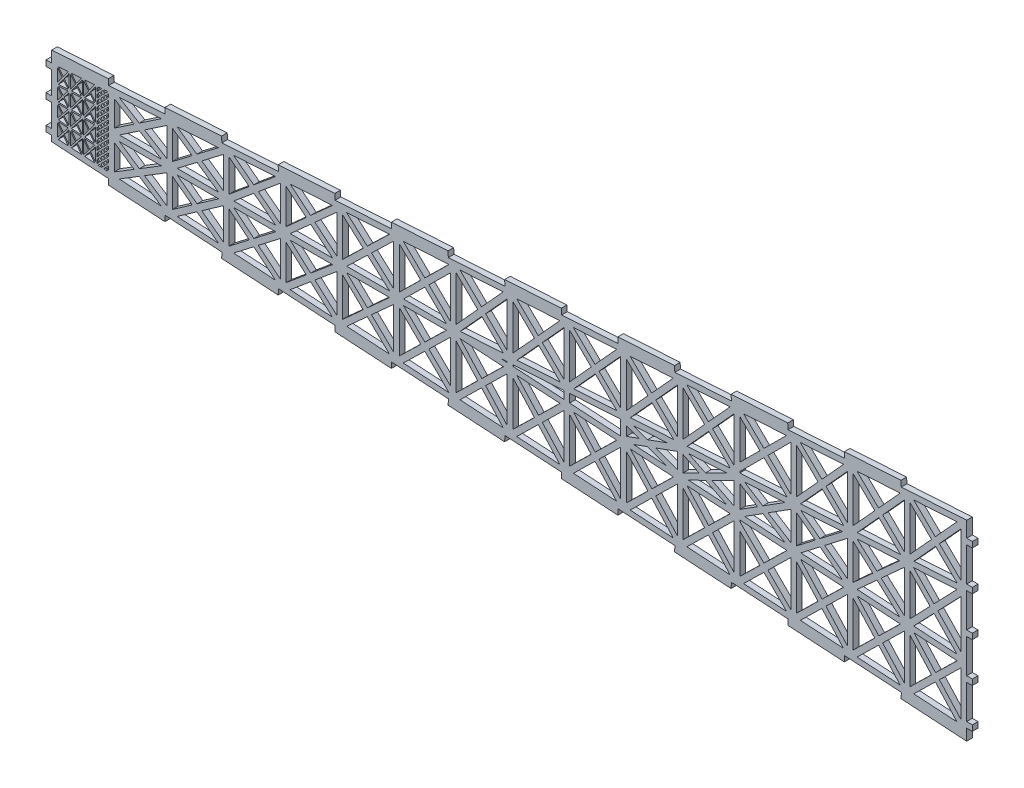
SolidWorks part; units mm, degrees
ref_plane "Front Plane" through (0, 0, 0) normal (0, 0, 1) x (1, 0, 0)
ref_plane "Top Plane" through (0, 0, 0) normal (0, 1, 0) x (1, 0, 0)
ref_plane "Right Plane" through (0, 0, 0) normal (1, 0, 0) x (0, 0, -1)
sketch "Sketch1" plane through (0, 0, 0) normal (0, 0, 1) x (1, 0, 0)
  line L1309 (16.6005, 125.1495) -> (19.3027, 128.3463)
  line L1310 (19.3027, 128.3463) -> (19.3027, 121.7873)
  line L1311 (19.3027, 121.7873) -> (16.6005, 125.1495)
  line L1312 (13.0834, 128.3286) -> (15.6287, 125.1616)
  line L1313 (15.6287, 125.1616) -> (13.0834, 122.1503)
  line L1314 (13.0834, 122.1503) -> (13.0834, 128.3286)
  line L1315 (18.7967, 121.2196) -> (13.5502, 121.5408)
  line L1316 (13.5502, 121.5408) -> (16.1073, 124.566)
  line L1317 (16.1073, 124.566) -> (18.7967, 121.2196)
  line L1318 (13.5645, 128.9272) -> (18.8117, 128.9272)
  line L1319 (18.8117, 128.9272) -> (16.1219, 125.7451)
  line L1320 (16.1219, 125.7451) -> (13.5645, 128.9272)
  line L1321 (16.664, 116.523) -> (19.3027, 119.8354)
  line L1322 (19.3027, 119.8354) -> (19.3027, 112.8875)
  line L1323 (19.3027, 112.8875) -> (16.664, 116.523)
  line L1324 (13.0834, 120.1796) -> (15.722, 116.5441)
  line L1325 (15.722, 116.5441) -> (13.0834, 113.2317)
  line L1326 (13.0834, 113.2317) -> (13.0834, 120.1796)
  line L1327 (13.5683, 120.7883) -> (18.8455, 120.4653)
  line L1328 (18.8455, 120.4653) -> (16.2069, 117.1528)
  line L1329 (16.2069, 117.1528) -> (13.5683, 120.7883)
  line L1330 (18.8178, 112.2788) -> (13.5405, 112.6018)
  line L1331 (13.5405, 112.6018) -> (16.1791, 115.9143)
  line L1332 (16.1791, 115.9143) -> (18.8178, 112.2788)
  line L1333 (23.6334, 116.0963) -> (26.272, 119.4087)
  line L1334 (26.272, 119.4087) -> (26.272, 112.4608)
  line L1335 (26.272, 112.4608) -> (23.6334, 116.0963)
  line L1336 (22.6913, 116.1174) -> (20.0527, 112.805)
  line L1337 (20.0527, 112.805) -> (20.0527, 119.7529)
  line L1338 (20.0527, 119.7529) -> (22.6913, 116.1174)
  line L1339 (20.5376, 120.3617) -> (25.8148, 120.0386)
  line L1340 (25.8148, 120.0386) -> (23.1762, 116.7262)
  line L1341 (23.1762, 116.7262) -> (20.5376, 120.3617)
  line L1342 (25.7871, 111.8521) -> (20.5098, 112.1752)
  line L1343 (20.5098, 112.1752) -> (23.1485, 115.4876)
  line L1344 (23.1485, 115.4876) -> (25.7871, 111.8521)
  line L1345 (23.5637, 124.9366) -> (26.272, 128.3265)
  line L1346 (26.272, 128.3265) -> (26.272, 121.3809)
  line L1347 (26.272, 121.3809) -> (23.5637, 124.9366)
  line L1348 (22.6125, 124.9476) -> (20.0527, 121.7435)
  line L1349 (20.0527, 121.7435) -> (20.0527, 128.3084)
  line L1350 (20.0527, 128.3084) -> (22.6125, 124.9476)
  line L1351 (25.7775, 120.7923) -> (20.5103, 121.1147)
  line L1352 (20.5103, 121.1147) -> (23.081, 124.3325)
  line L1353 (23.081, 124.3325) -> (25.7775, 120.7923)
  line L1354 (20.5241, 128.9272) -> (25.792, 128.9272)
  line L1355 (25.792, 128.9272) -> (23.0952, 125.5517)
  line L1356 (23.0952, 125.5517) -> (20.5241, 128.9272)
  line L1357 (30.5278, 124.7236) -> (33.2413, 128.3062)
  line L1358 (33.2413, 128.3062) -> (33.2413, 120.9749)
  line L1359 (33.2413, 120.9749) -> (30.5278, 124.7236)
  line L1360 (29.5946, 124.7337) -> (27.022, 121.3372)
  line L1361 (27.022, 121.3372) -> (27.022, 128.2877)
  line L1362 (27.022, 128.2877) -> (29.5946, 124.7337)
  line L1363 (32.7569, 120.365) -> (27.4716, 120.6886)
  line L1364 (27.4716, 120.6886) -> (30.0544, 124.0985)
  line L1365 (30.0544, 124.0985) -> (32.7569, 120.365)
  line L1366 (27.4849, 128.9272) -> (32.7709, 128.9272)
  line L1367 (32.7709, 128.9272) -> (30.068, 125.3587)
  line L1368 (30.068, 125.3587) -> (27.4849, 128.9272)
  line L1369 (30.6027, 115.6697) -> (33.2413, 118.9821)
  line L1370 (33.2413, 118.9821) -> (33.2413, 112.0342)
  line L1371 (33.2413, 112.0342) -> (30.6027, 115.6697)
  line L1372 (29.6606, 115.6908) -> (27.022, 112.3784)
  line L1373 (27.022, 112.3784) -> (27.022, 119.3263)
  line L1374 (27.022, 119.3263) -> (29.6606, 115.6908)
  line L1375 (27.5069, 119.935) -> (32.7842, 119.6119)
  line L1376 (32.7842, 119.6119) -> (30.1455, 116.2995)
  line L1377 (30.1455, 116.2995) -> (27.5069, 119.935)
  line L1378 (32.7564, 111.4255) -> (27.4791, 111.7485)
  line L1379 (27.4791, 111.7485) -> (30.1178, 115.0609)
  line L1380 (30.1178, 115.0609) -> (32.7564, 111.4255)
  line L1381 (16.6005, 133.455) -> (19.3027, 136.8172)
  line L1382 (19.3027, 136.8172) -> (19.3027, 130.2581)
  line L1383 (19.3027, 130.2581) -> (16.6005, 133.455)
  line L1384 (13.0834, 136.4542) -> (13.0834, 130.2759)
  line L1385 (13.0834, 130.2759) -> (15.6287, 133.4429)
  line L1386 (15.6287, 133.4429) -> (13.0834, 136.4542)
  line L1387 (13.5502, 137.0637) -> (18.7967, 137.3848)
  line L1388 (18.7967, 137.3848) -> (16.1073, 134.0385)
  line L1389 (16.1073, 134.0385) -> (13.5502, 137.0637)
  line L1390 (18.8117, 129.6772) -> (13.5645, 129.6772)
  line L1391 (13.5645, 129.6772) -> (16.1219, 132.8594)
  line L1392 (16.1219, 132.8594) -> (18.8117, 129.6772)
  line L1393 (16.664, 142.0815) -> (19.3027, 145.717)
  line L1394 (19.3027, 145.717) -> (19.3027, 138.7691)
  line L1395 (19.3027, 138.7691) -> (16.664, 142.0815)
  line L1396 (13.0834, 145.3728) -> (15.722, 142.0604)
  line L1397 (15.722, 142.0604) -> (13.0834, 138.4249)
  line L1398 (13.0834, 138.4249) -> (13.0834, 145.3728)
  line L1399 (18.8455, 138.1392) -> (13.5683, 137.8162)
  line L1400 (13.5683, 137.8162) -> (16.2069, 141.4517)
  line L1401 (16.2069, 141.4517) -> (18.8455, 138.1392)
  line L1402 (13.5405, 146.0027) -> (18.8178, 146.3257)
  line L1403 (18.8178, 146.3257) -> (16.1791, 142.6902)
  line L1404 (16.1791, 142.6902) -> (13.5405, 146.0027)
  line L1405 (22.6125, 133.6569) -> (20.0527, 130.2961)
  line L1406 (20.0527, 130.2961) -> (20.0527, 136.861)
  line L1407 (20.0527, 136.861) -> (22.6125, 133.6569)
  line L1408 (23.5637, 133.6679) -> (26.272, 137.2236)
  line L1409 (26.272, 137.2236) -> (26.272, 130.278)
  line L1410 (26.272, 130.278) -> (23.5637, 133.6679)
  line L1411 (20.5103, 137.4897) -> (25.7775, 137.8122)
  line L1412 (25.7775, 137.8122) -> (23.081, 134.272)
  line L1413 (23.081, 134.272) -> (20.5103, 137.4897)
  line L1414 (25.792, 129.6772) -> (20.5241, 129.6772)
  line L1415 (20.5241, 129.6772) -> (23.0952, 133.0528)
  line L1416 (23.0952, 133.0528) -> (25.792, 129.6772)
  line L1417 (22.6913, 142.487) -> (20.0527, 138.8516)
  line L1418 (20.0527, 138.8516) -> (20.0527, 145.7995)
  line L1419 (20.0527, 145.7995) -> (22.6913, 142.487)
  line L1420 (23.6334, 142.5082) -> (26.272, 146.1437)
  line L1421 (26.272, 146.1437) -> (26.272, 139.1957)
  line L1422 (26.272, 139.1957) -> (23.6334, 142.5082)
  line L1423 (25.8148, 138.5659) -> (20.5376, 138.2428)
  line L1424 (20.5376, 138.2428) -> (23.1762, 141.8783)
  line L1425 (23.1762, 141.8783) -> (25.8148, 138.5659)
  line L1426 (20.5098, 146.4293) -> (25.7871, 146.7524)
  line L1427 (25.7871, 146.7524) -> (23.1485, 143.1169)
  line L1428 (23.1485, 143.1169) -> (20.5098, 146.4293)
  line L1429 (30.5278, 133.8809) -> (33.2413, 137.6296)
  line L1430 (33.2413, 137.6296) -> (33.2413, 130.2983)
  line L1431 (33.2413, 130.2983) -> (30.5278, 133.8809)
  line L1432 (29.5946, 133.8708) -> (27.022, 130.3168)
  line L1433 (27.022, 130.3168) -> (27.022, 137.2673)
  line L1434 (27.022, 137.2673) -> (29.5946, 133.8708)
  line L1435 (27.4716, 137.9159) -> (32.7569, 138.2395)
  line L1436 (32.7569, 138.2395) -> (30.0544, 134.5059)
  line L1437 (30.0544, 134.5059) -> (27.4716, 137.9159)
  line L1438 (32.7709, 129.6772) -> (27.4849, 129.6772)
  line L1439 (27.4849, 129.6772) -> (30.068, 133.2457)
  line L1440 (30.068, 133.2457) -> (32.7709, 129.6772)
  line L1441 (30.6027, 142.9348) -> (33.2413, 146.5703)
  line L1442 (33.2413, 146.5703) -> (33.2413, 139.6224)
  line L1443 (33.2413, 139.6224) -> (30.6027, 142.9348)
  line L1444 (27.4791, 146.856) -> (32.7564, 147.179)
  line L1445 (32.7564, 147.179) -> (30.1178, 143.5435)
  line L1446 (30.1178, 143.5435) -> (27.4791, 146.856)
  line L1447 (29.6606, 142.9137) -> (27.022, 139.2782)
  line L1448 (27.022, 139.2782) -> (27.022, 146.2261)
  line L1449 (27.022, 146.2261) -> (29.6606, 142.9137)
  line L1450 (32.7842, 138.9926) -> (27.5069, 138.6695)
  line L1451 (27.5069, 138.6695) -> (30.1455, 142.305)
  line L1452 (30.1455, 142.305) -> (32.7842, 138.9926)
  line L1453 (38.601, 128.3326) -> (37.6313, 129.3022)
  line L1454 (37.6313, 129.3022) -> (38.601, 130.2719)
  line L1455 (38.601, 130.2719) -> (39.5706, 129.3022)
  line L1456 (39.5706, 129.3022) -> (38.601, 128.3326)
  line L1457 (37.101, 126.8326) -> (36.1313, 127.8022)
  line L1458 (36.1313, 127.8022) -> (37.101, 128.7719)
  line L1459 (37.101, 128.7719) -> (38.0706, 127.8022)
  line L1460 (38.0706, 127.8022) -> (37.101, 126.8326)
  line L1461 (35.601, 125.3326) -> (34.6313, 126.3022)
  line L1462 (34.6313, 126.3022) -> (35.601, 127.2719)
  line L1463 (35.601, 127.2719) -> (36.5706, 126.3022)
  line L1464 (36.5706, 126.3022) -> (35.601, 125.3326)
  line L1465 (34.101, 123.8326) -> (33.9913, 123.9422)
  line L1466 (33.9913, 123.9422) -> (33.9913, 125.6623)
  line L1467 (33.9913, 125.6623) -> (34.101, 125.7719)
  line L1468 (34.101, 125.7719) -> (35.0706, 124.8022)
  line L1469 (35.0706, 124.8022) -> (34.101, 123.8326)
  line L1470 (40.2106, 129.9422) -> (40.101, 129.8326)
  line L1471 (40.101, 129.8326) -> (39.1313, 130.8022)
  line L1472 (39.1313, 130.8022) -> (40.101, 131.7719)
  line L1473 (40.101, 131.7719) -> (40.2106, 131.6623)
  line L1474 (40.2106, 131.6623) -> (40.2106, 129.9422)
  line L1475 (38.601, 125.3326) -> (37.6313, 126.3022)
  line L1476 (37.6313, 126.3022) -> (38.601, 127.2719)
  line L1477 (38.601, 127.2719) -> (39.5706, 126.3022)
  line L1478 (39.5706, 126.3022) -> (38.601, 125.3326)
  line L1479 (37.101, 123.8326) -> (36.1313, 124.8022)
  line L1480 (36.1313, 124.8022) -> (37.101, 125.7719)
  line L1481 (37.101, 125.7719) -> (38.0706, 124.8022)
  line L1482 (38.0706, 124.8022) -> (37.101, 123.8326)
  line L1483 (35.601, 122.3326) -> (34.6313, 123.3022)
  line L1484 (34.6313, 123.3022) -> (35.601, 124.2719)
  line L1485 (35.601, 124.2719) -> (36.5706, 123.3022)
  line L1486 (36.5706, 123.3022) -> (35.601, 122.3326)
  line L1487 (34.101, 120.8326) -> (33.9913, 120.9422)
  line L1488 (33.9913, 120.9422) -> (33.9913, 122.6623)
  line L1489 (33.9913, 122.6623) -> (34.101, 122.7719)
  line L1490 (34.101, 122.7719) -> (35.0706, 121.8022)
  line L1491 (35.0706, 121.8022) -> (34.101, 120.8326)
  line L1492 (40.2106, 126.9422) -> (40.101, 126.8326)
  line L1493 (40.101, 126.8326) -> (39.1313, 127.8022)
  line L1494 (39.1313, 127.8022) -> (40.101, 128.7719)
  line L1495 (40.101, 128.7719) -> (40.2106, 128.6623)
  line L1496 (40.2106, 128.6623) -> (40.2106, 126.9422)
  line L1497 (38.601, 122.3326) -> (37.6313, 123.3022)
  line L1498 (37.6313, 123.3022) -> (38.601, 124.2719)
  line L1499 (38.601, 124.2719) -> (39.5706, 123.3022)
  line L1500 (39.5706, 123.3022) -> (38.601, 122.3326)
  line L1501 (37.101, 120.8326) -> (36.1313, 121.8022)
  line L1502 (36.1313, 121.8022) -> (37.101, 122.7719)
  line L1503 (37.101, 122.7719) -> (38.0706, 121.8022)
  line L1504 (38.0706, 121.8022) -> (37.101, 120.8326)
  line L1505 (35.601, 119.3326) -> (34.6313, 120.3022)
  line L1506 (34.6313, 120.3022) -> (35.601, 121.2719)
  line L1507 (35.601, 121.2719) -> (36.5706, 120.3022)
  line L1508 (36.5706, 120.3022) -> (35.601, 119.3326)
  line L1509 (34.101, 117.8326) -> (33.9913, 117.9422)
  line L1510 (33.9913, 117.9422) -> (33.9913, 119.6623)
  line L1511 (33.9913, 119.6623) -> (34.101, 119.7719)
  line L1512 (34.101, 119.7719) -> (35.0706, 118.8022)
  line L1513 (35.0706, 118.8022) -> (34.101, 117.8326)
  line L1514 (40.2106, 123.9422) -> (40.101, 123.8326)
  line L1515 (40.101, 123.8326) -> (39.1313, 124.8022)
  line L1516 (39.1313, 124.8022) -> (40.101, 125.7719)
  line L1517 (40.101, 125.7719) -> (40.2106, 125.6623)
  line L1518 (40.2106, 125.6623) -> (40.2106, 123.9422)
  line L1519 (38.601, 119.3326) -> (37.6313, 120.3022)
  line L1520 (37.6313, 120.3022) -> (38.601, 121.2719)
  line L1521 (38.601, 121.2719) -> (39.5706, 120.3022)
  line L1522 (39.5706, 120.3022) -> (38.601, 119.3326)
  line L1523 (37.101, 117.8326) -> (36.1313, 118.8022)
  line L1524 (36.1313, 118.8022) -> (37.101, 119.7719)
  line L1525 (37.101, 119.7719) -> (38.0706, 118.8022)
  line L1526 (38.0706, 118.8022) -> (37.101, 117.8326)
  line L1527 (35.601, 116.3326) -> (34.6313, 117.3022)
  line L1528 (34.6313, 117.3022) -> (35.601, 118.2719)
  line L1529 (35.601, 118.2719) -> (36.5706, 117.3022)
  line L1530 (36.5706, 117.3022) -> (35.601, 116.3326)
  line L1531 (34.101, 114.8326) -> (33.9913, 114.9422)
  line L1532 (33.9913, 114.9422) -> (33.9913, 116.6623)
  line L1533 (33.9913, 116.6623) -> (34.101, 116.7719)
  line L1534 (34.101, 116.7719) -> (35.0706, 115.8022)
  line L1535 (35.0706, 115.8022) -> (34.101, 114.8326)
  line L1536 (40.2106, 120.9422) -> (40.101, 120.8326)
  line L1537 (40.101, 120.8326) -> (39.1313, 121.8022)
  line L1538 (39.1313, 121.8022) -> (40.101, 122.7719)
  line L1539 (40.101, 122.7719) -> (40.2106, 122.6623)
  line L1540 (40.2106, 122.6623) -> (40.2106, 120.9422)
  line L1541 (38.601, 116.3326) -> (37.6313, 117.3022)
  line L1542 (37.6313, 117.3022) -> (38.601, 118.2719)
  line L1543 (38.601, 118.2719) -> (39.5706, 117.3022)
  line L1544 (39.5706, 117.3022) -> (38.601, 116.3326)
  line L1545 (37.101, 114.8326) -> (36.1313, 115.8022)
  line L1546 (36.1313, 115.8022) -> (37.101, 116.7719)
  line L1547 (37.101, 116.7719) -> (38.0706, 115.8022)
  line L1548 (38.0706, 115.8022) -> (37.101, 114.8326)
  line L1549 (35.601, 113.3326) -> (34.6313, 114.3022)
  line L1550 (34.6313, 114.3022) -> (35.601, 115.2719)
  line L1551 (35.601, 115.2719) -> (36.5706, 114.3022)
  line L1552 (36.5706, 114.3022) -> (35.601, 113.3326)
  line L1553 (34.101, 111.8326) -> (33.9913, 111.9422)
  line L1554 (33.9913, 111.9422) -> (33.9913, 113.6623)
  line L1555 (33.9913, 113.6623) -> (34.101, 113.7719)
  line L1556 (34.101, 113.7719) -> (35.0706, 112.8022)
  line L1557 (35.0706, 112.8022) -> (34.101, 111.8326)
  line L1558 (40.2106, 117.9422) -> (40.101, 117.8326)
  line L1559 (40.101, 117.8326) -> (39.1313, 118.8022)
  line L1560 (39.1313, 118.8022) -> (40.101, 119.7719)
  line L1561 (40.101, 119.7719) -> (40.2106, 119.6623)
  line L1562 (40.2106, 119.6623) -> (40.2106, 117.9422)
  line L1563 (38.601, 113.3326) -> (37.6313, 114.3022)
  line L1564 (37.6313, 114.3022) -> (38.601, 115.2719)
  line L1565 (38.601, 115.2719) -> (39.5706, 114.3022)
  line L1566 (39.5706, 114.3022) -> (38.601, 113.3326)
  line L1567 (37.101, 111.8326) -> (36.1313, 112.8022)
  line L1568 (36.1313, 112.8022) -> (37.101, 113.7719)
  line L1569 (37.101, 113.7719) -> (38.0706, 112.8022)
  line L1570 (38.0706, 112.8022) -> (37.101, 111.8326)
  line L1571 (36.4667, 111.1983) -> (34.6392, 111.3102)
  line L1572 (34.6392, 111.3102) -> (35.601, 112.2719)
  line L1573 (35.601, 112.2719) -> (36.5706, 111.3022)
  line L1574 (36.5706, 111.3022) -> (36.4667, 111.1983)
  line L1575 (40.2106, 114.9422) -> (40.101, 114.8326)
  line L1576 (40.101, 114.8326) -> (39.1313, 115.8022)
  line L1577 (39.1313, 115.8022) -> (40.101, 116.7719)
  line L1578 (40.101, 116.7719) -> (40.2106, 116.6623)
  line L1579 (40.2106, 116.6623) -> (40.2106, 114.9422)
  line L1580 (39.2936, 111.0252) -> (37.8179, 111.1156)
  line L1581 (37.8179, 111.1156) -> (37.6313, 111.3022)
  line L1582 (37.6313, 111.3022) -> (38.601, 112.2719)
  line L1583 (38.601, 112.2719) -> (39.5706, 111.3022)
  line L1584 (39.5706, 111.3022) -> (39.2936, 111.0252)
  line L1585 (40.2106, 111.9422) -> (40.101, 111.8326)
  line L1586 (40.101, 111.8326) -> (39.1313, 112.8022)
  line L1587 (39.1313, 112.8022) -> (40.101, 113.7719)
  line L1588 (40.101, 113.7719) -> (40.2106, 113.6623)
  line L1589 (40.2106, 113.6623) -> (40.2106, 111.9422)
  line L1590 (40.101, 134.7719) -> (40.2106, 134.6623)
  line L1591 (40.2106, 134.6623) -> (40.2106, 132.9422)
  line L1592 (40.2106, 132.9422) -> (40.101, 132.8326)
  line L1593 (40.101, 132.8326) -> (39.1313, 133.8022)
  line L1594 (39.1313, 133.8022) -> (40.101, 134.7719)
  line L1595 (37.6313, 132.3022) -> (38.601, 133.2719)
  line L1596 (38.601, 133.2719) -> (39.5706, 132.3022)
  line L1597 (39.5706, 132.3022) -> (38.601, 131.3326)
  line L1598 (38.601, 131.3326) -> (37.6313, 132.3022)
  line L1599 (36.1313, 130.8022) -> (37.101, 131.7719)
  line L1600 (37.101, 131.7719) -> (38.0706, 130.8022)
  line L1601 (38.0706, 130.8022) -> (37.101, 129.8326)
  line L1602 (37.101, 129.8326) -> (36.1313, 130.8022)
  line L1603 (34.101, 128.7719) -> (35.0706, 127.8022)
  line L1604 (35.0706, 127.8022) -> (34.101, 126.8326)
  line L1605 (34.101, 126.8326) -> (33.9913, 126.9422)
  line L1606 (33.9913, 126.9422) -> (33.9913, 128.6623)
  line L1607 (33.9913, 128.6623) -> (34.101, 128.7719)
  line L1608 (35.601, 130.2719) -> (36.5706, 129.3022)
  line L1609 (36.5706, 129.3022) -> (35.601, 128.3326)
  line L1610 (35.601, 128.3326) -> (34.6313, 129.3022)
  line L1611 (34.6313, 129.3022) -> (35.601, 130.2719)
  line L1612 (40.101, 137.7719) -> (40.2106, 137.6623)
  line L1613 (40.2106, 137.6623) -> (40.2106, 135.9422)
  line L1614 (40.2106, 135.9422) -> (40.101, 135.8326)
  line L1615 (40.101, 135.8326) -> (39.1313, 136.8022)
  line L1616 (39.1313, 136.8022) -> (40.101, 137.7719)
  line L1617 (37.6313, 135.3022) -> (38.601, 136.2719)
  line L1618 (38.601, 136.2719) -> (39.5706, 135.3022)
  line L1619 (39.5706, 135.3022) -> (38.601, 134.3326)
  line L1620 (38.601, 134.3326) -> (37.6313, 135.3022)
  line L1621 (36.1313, 133.8022) -> (37.101, 134.7719)
  line L1622 (37.101, 134.7719) -> (38.0706, 133.8022)
  line L1623 (38.0706, 133.8022) -> (37.101, 132.8326)
  line L1624 (37.101, 132.8326) -> (36.1313, 133.8022)
  line L1625 (34.6313, 132.3022) -> (35.601, 133.2719)
  line L1626 (35.601, 133.2719) -> (36.5706, 132.3022)
  line L1627 (36.5706, 132.3022) -> (35.601, 131.3326)
  line L1628 (35.601, 131.3326) -> (34.6313, 132.3022)
  line L1629 (34.101, 131.7719) -> (35.0706, 130.8022)
  line L1630 (35.0706, 130.8022) -> (34.101, 129.8326)
  line L1631 (34.101, 129.8326) -> (33.9913, 129.9422)
  line L1632 (33.9913, 129.9422) -> (33.9913, 131.6623)
  line L1633 (33.9913, 131.6623) -> (34.101, 131.7719)
  line L1634 (40.101, 140.7719) -> (40.2106, 140.6623)
  line L1635 (40.2106, 140.6623) -> (40.2106, 138.9422)
  line L1636 (40.2106, 138.9422) -> (40.101, 138.8326)
  line L1637 (40.101, 138.8326) -> (39.1313, 139.8022)
  line L1638 (39.1313, 139.8022) -> (40.101, 140.7719)
  line L1639 (37.6313, 138.3022) -> (38.601, 139.2719)
  line L1640 (38.601, 139.2719) -> (39.5706, 138.3022)
  line L1641 (39.5706, 138.3022) -> (38.601, 137.3326)
  line L1642 (38.601, 137.3326) -> (37.6313, 138.3022)
  line L1643 (36.1313, 136.8022) -> (37.101, 137.7719)
  line L1644 (37.101, 137.7719) -> (38.0706, 136.8022)
  line L1645 (38.0706, 136.8022) -> (37.101, 135.8326)
  line L1646 (37.101, 135.8326) -> (36.1313, 136.8022)
  line L1647 (34.6313, 135.3022) -> (35.601, 136.2719)
  line L1648 (35.601, 136.2719) -> (36.5706, 135.3022)
  line L1649 (36.5706, 135.3022) -> (35.601, 134.3326)
  line L1650 (35.601, 134.3326) -> (34.6313, 135.3022)
  line L1651 (34.101, 134.7719) -> (35.0706, 133.8022)
  line L1652 (35.0706, 133.8022) -> (34.101, 132.8326)
  line L1653 (34.101, 132.8326) -> (33.9913, 132.9422)
  line L1654 (33.9913, 132.9422) -> (33.9913, 134.6623)
  line L1655 (33.9913, 134.6623) -> (34.101, 134.7719)
  line L1656 (40.101, 143.7719) -> (40.2106, 143.6623)
  line L1657 (40.2106, 143.6623) -> (40.2106, 141.9422)
  line L1658 (40.2106, 141.9422) -> (40.101, 141.8326)
  line L1659 (40.101, 141.8326) -> (39.1313, 142.8022)
  line L1660 (39.1313, 142.8022) -> (40.101, 143.7719)
  line L1661 (37.6313, 141.3022) -> (38.601, 142.2719)
  line L1662 (38.601, 142.2719) -> (39.5706, 141.3022)
  line L1663 (39.5706, 141.3022) -> (38.601, 140.3326)
  line L1664 (38.601, 140.3326) -> (37.6313, 141.3022)
  line L1665 (36.1313, 139.8022) -> (37.101, 140.7719)
  line L1666 (37.101, 140.7719) -> (38.0706, 139.8022)
  line L1667 (38.0706, 139.8022) -> (37.101, 138.8326)
  line L1668 (37.101, 138.8326) -> (36.1313, 139.8022)
  line L1669 (34.6313, 138.3022) -> (35.601, 139.2719)
  line L1670 (35.601, 139.2719) -> (36.5706, 138.3022)
  line L1671 (36.5706, 138.3022) -> (35.601, 137.3326)
  line L1672 (35.601, 137.3326) -> (34.6313, 138.3022)
  line L1673 (34.101, 137.7719) -> (35.0706, 136.8022)
  line L1674 (35.0706, 136.8022) -> (34.101, 135.8326)
  line L1675 (34.101, 135.8326) -> (33.9913, 135.9422)
  line L1676 (33.9913, 135.9422) -> (33.9913, 137.6623)
  line L1677 (33.9913, 137.6623) -> (34.101, 137.7719)
  line L1678 (40.101, 146.7719) -> (40.2106, 146.6623)
  line L1679 (40.2106, 146.6623) -> (40.2106, 144.9422)
  line L1680 (40.2106, 144.9422) -> (40.101, 144.8326)
  line L1681 (40.101, 144.8326) -> (39.1313, 145.8022)
  line L1682 (39.1313, 145.8022) -> (40.101, 146.7719)
  line L1683 (37.6313, 144.3022) -> (38.601, 145.2719)
  line L1684 (38.601, 145.2719) -> (39.5706, 144.3022)
  line L1685 (39.5706, 144.3022) -> (38.601, 143.3326)
  line L1686 (38.601, 143.3326) -> (37.6313, 144.3022)
  line L1687 (36.1313, 142.8022) -> (37.101, 143.7719)
  line L1688 (37.101, 143.7719) -> (38.0706, 142.8022)
  line L1689 (38.0706, 142.8022) -> (37.101, 141.8326)
  line L1690 (37.101, 141.8326) -> (36.1313, 142.8022)
  line L1691 (34.6313, 141.3022) -> (35.601, 142.2719)
  line L1692 (35.601, 142.2719) -> (36.5706, 141.3022)
  line L1693 (36.5706, 141.3022) -> (35.601, 140.3326)
  line L1694 (35.601, 140.3326) -> (34.6313, 141.3022)
  line L1695 (34.101, 140.7719) -> (35.0706, 139.8022)
  line L1696 (35.0706, 139.8022) -> (34.101, 138.8326)
  line L1697 (34.101, 138.8326) -> (33.9913, 138.9422)
  line L1698 (33.9913, 138.9422) -> (33.9913, 140.6623)
  line L1699 (33.9913, 140.6623) -> (34.101, 140.7719)
  line L1700 (37.8179, 147.4889) -> (39.2936, 147.5792)
  line L1701 (39.2936, 147.5792) -> (39.5706, 147.3022)
  line L1702 (39.5706, 147.3022) -> (38.601, 146.3326)
  line L1703 (38.601, 146.3326) -> (37.6313, 147.3022)
  line L1704 (37.6313, 147.3022) -> (37.8179, 147.4889)
  line L1705 (36.1313, 145.8022) -> (37.101, 146.7719)
  line L1706 (37.101, 146.7719) -> (38.0706, 145.8022)
  line L1707 (38.0706, 145.8022) -> (37.101, 144.8326)
  line L1708 (37.101, 144.8326) -> (36.1313, 145.8022)
  line L1709 (34.6313, 144.3022) -> (35.601, 145.2719)
  line L1710 (35.601, 145.2719) -> (36.5706, 144.3022)
  line L1711 (36.5706, 144.3022) -> (35.601, 143.3326)
  line L1712 (35.601, 143.3326) -> (34.6313, 144.3022)
  line L1713 (35.601, 146.3326) -> (34.6392, 147.2943)
  line L1714 (34.6392, 147.2943) -> (36.4667, 147.4062)
  line L1715 (36.4667, 147.4062) -> (36.5706, 147.3022)
  line L1716 (36.5706, 147.3022) -> (35.601, 146.3326)
  line L1717 (34.101, 143.7719) -> (35.0706, 142.8022)
  line L1718 (35.0706, 142.8022) -> (34.101, 141.8326)
  line L1719 (34.101, 141.8326) -> (33.9913, 141.9422)
  line L1720 (33.9913, 141.9422) -> (33.9913, 143.6623)
  line L1721 (33.9913, 143.6623) -> (34.101, 143.7719)
  line L1722 (34.101, 146.7719) -> (35.0706, 145.8022)
  line L1723 (35.0706, 145.8022) -> (34.101, 144.8326)
  line L1724 (34.101, 144.8326) -> (33.9913, 144.9422)
  line L1725 (33.9913, 144.9422) -> (33.9913, 146.6623)
  line L1726 (33.9913, 146.6623) -> (34.101, 146.7719)
  line L1727 (284, 127.0808) -> (284, 131.5237)
  line L1728 (284, 131.5237) -> (311, 133.1766)
  line L1729 (311, 133.1766) -> (311, 125.4278)
  line L1730 (311, 125.4278) -> (284, 127.0808)
  line L1731 (254, 128.9173) -> (254, 129.6871)
  line L1732 (254, 129.6871) -> (281, 131.3401)
  line L1733 (281, 131.3401) -> (281, 127.2644)
  line L1734 (281, 127.2644) -> (254, 128.9173)
  line L1735 (251, 129.5035) -> (247.7127, 129.3022)
  line L1736 (247.7127, 129.3022) -> (251, 129.101)
  line L1737 (251, 129.101) -> (251, 129.5035)
  line L1738 (114.5786, 117.0807) -> (104, 108.9554)
  line L1739 (104, 108.9554) -> (104, 125.8535)
  line L1740 (104, 125.8535) -> (114.5786, 117.0807)
  line L1741 (98.3845, 127.8022) -> (76.4764, 127.8022)
  line L1742 (76.4764, 127.8022) -> (86.9715, 119.8125)
  line L1743 (86.9715, 119.8125) -> (98.3845, 127.8022)
  line L1744 (101, 109.1328) -> (89.4775, 117.9047)
  line L1745 (89.4775, 117.9047) -> (101, 125.9712)
  line L1746 (101, 125.9712) -> (101, 109.1328)
  line L1747 (43.2106, 125.9937) -> (43.2106, 112.5443)
  line L1748 (43.2106, 112.5443) -> (53.6696, 118.9489)
  line L1749 (53.6696, 118.9489) -> (43.2106, 125.9937)
  line L1750 (71, 126.0434) -> (71, 110.8927)
  line L1751 (71, 110.8927) -> (59.218, 118.8287)
  line L1752 (59.218, 118.8287) -> (71, 126.0434)
  line L1753 (84.3914, 118.0062) -> (74, 110.7316)
  line L1754 (74, 110.7316) -> (74, 125.917)
  line L1755 (74, 125.917) -> (84.3914, 118.0062)
  line L1756 (98.3071, 107.4125) -> (76.4052, 108.7533)
  line L1757 (76.4052, 108.7533) -> (86.8974, 116.0985)
  line L1758 (86.8974, 116.0985) -> (98.3071, 107.4125)
  line L1759 (131, 125.9108) -> (131, 107.3598)
  line L1760 (131, 107.3598) -> (119.3866, 116.9908)
  line L1761 (119.3866, 116.9908) -> (131, 125.9108)
  line L1762 (128.5375, 127.8022) -> (117.0185, 118.9547)
  line L1763 (117.0185, 118.9547) -> (106.3498, 127.8022)
  line L1764 (106.3498, 127.8022) -> (128.5375, 127.8022)
  line L1765 (106.2807, 106.9244) -> (116.9467, 115.1168)
  line L1766 (116.9467, 115.1168) -> (128.4629, 105.5664)
  line L1767 (128.4629, 105.5664) -> (106.2807, 106.9244)
  line L1768 (68.1276, 127.8022) -> (56.4824, 120.6713)
  line L1769 (56.4824, 120.6713) -> (45.8956, 127.8022)
  line L1770 (45.8956, 127.8022) -> (68.1276, 127.8022)
  line L1771 (45.8219, 110.6256) -> (56.4052, 117.1063)
  line L1772 (56.4052, 117.1063) -> (68.0466, 109.265)
  line L1773 (68.0466, 109.265) -> (45.8219, 110.6256)
  line L1774 (475.4164, 98.2754) -> (464, 87.1221)
  line L1775 (464, 87.1221) -> (464, 110.8265)
  line L1776 (464, 110.8265) -> (475.4164, 98.2754)
  line L1777 (488.9801, 111.5264) -> (477.5637, 100.3731)
  line L1778 (477.5637, 100.3731) -> (466.1473, 112.9242)
  line L1779 (466.1473, 112.9242) -> (488.9801, 111.5264)
  line L1780 (461, 87.4379) -> (449.5836, 99.989)
  line L1781 (449.5836, 99.989) -> (461, 111.1423)
  line L1782 (461, 111.1423) -> (461, 87.4379)
  line L1783 (415.4164, 101.9485) -> (404, 90.7952)
  line L1784 (404, 90.7952) -> (404, 114.4996)
  line L1785 (404, 114.4996) -> (415.4164, 101.9485)
  line L1786 (428.9801, 115.1996) -> (417.5637, 104.0463)
  line L1787 (417.5637, 104.0463) -> (406.1473, 116.5974)
  line L1788 (406.1473, 116.5974) -> (428.9801, 115.1996)
  line L1789 (386.7994, 105.1362) -> (374, 117.879)
  line L1790 (374, 117.879) -> (374, 118.5654)
  line L1791 (374, 118.5654) -> (398.9801, 117.0362)
  line L1792 (398.9801, 117.0362) -> (386.7994, 105.1362)
  line L1793 (401, 90.9985) -> (388.9256, 103.0194)
  line L1794 (388.9256, 103.0194) -> (401, 114.8155)
  line L1795 (401, 114.8155) -> (401, 90.9985)
  line L1796 (355.4164, 105.6217) -> (344, 94.4684)
  line L1797 (344, 94.4684) -> (344, 118.1728)
  line L1798 (344, 118.1728) -> (355.4164, 105.6217)
  line L1799 (368.9801, 118.8727) -> (357.5637, 107.7194)
  line L1800 (357.5637, 107.7194) -> (346.1473, 120.2705)
  line L1801 (346.1473, 120.2705) -> (368.9801, 118.8727)
  line L1802 (341, 94.7843) -> (329.5836, 107.3353)
  line L1803 (329.5836, 107.3353) -> (341, 118.4886)
  line L1804 (341, 118.4886) -> (341, 94.7843)
  line L1805 (295.4164, 109.2948) -> (284, 98.1415)
  line L1806 (284, 98.1415) -> (284, 121.8459)
  line L1807 (284, 121.8459) -> (295.4164, 109.2948)
  line L1808 (308.9801, 122.5459) -> (297.5637, 111.3926)
  line L1809 (297.5637, 111.3926) -> (286.1473, 123.9437)
  line L1810 (286.1473, 123.9437) -> (308.9801, 122.5459)
  line L1811 (281, 98.4574) -> (269.5836, 111.0085)
  line L1812 (269.5836, 111.0085) -> (281, 122.1618)
  line L1813 (281, 122.1618) -> (281, 98.4574)
  line L1814 (235.4164, 112.968) -> (224, 101.8147)
  line L1815 (224, 101.8147) -> (224, 125.5191)
  line L1816 (224, 125.5191) -> (235.4164, 112.968)
  line L1817 (248.9801, 126.219) -> (237.5637, 115.0658)
  line L1818 (237.5637, 115.0658) -> (226.1473, 127.6168)
  line L1819 (226.1473, 127.6168) -> (248.9801, 126.219)
  line L1820 (218.8481, 127.8022) -> (196.1412, 127.8022)
  line L1821 (196.1412, 127.8022) -> (207.4395, 116.7114)
  line L1822 (207.4395, 116.7114) -> (218.8481, 127.8022)
  line L1823 (221, 103.3999) -> (209.581, 114.6093)
  line L1824 (209.581, 114.6093) -> (221, 125.7103)
  line L1825 (221, 125.7103) -> (221, 103.3999)
  line L1826 (174.861, 115.2327) -> (164, 105.413)
  line L1827 (164, 105.413) -> (164, 125.7174)
  line L1828 (164, 125.7174) -> (174.861, 115.2327)
  line L1829 (161, 105.5898) -> (149.3138, 116.0761)
  line L1830 (149.3138, 116.0761) -> (161, 125.847)
  line L1831 (161, 125.847) -> (161, 105.5898)
  line L1832 (136.246, 127.8022) -> (158.6615, 127.8022)
  line L1833 (158.6615, 127.8022) -> (147.0579, 118.1004)
  line L1834 (147.0579, 118.1004) -> (136.246, 127.8022)
  line L1835 (144.7326, 116.1562) -> (134, 107.1826)
  line L1836 (134, 107.1826) -> (134, 125.7869)
  line L1837 (134, 125.7869) -> (144.7326, 116.1562)
  line L1838 (158.5896, 103.722) -> (136.179, 105.094)
  line L1839 (136.179, 105.094) -> (146.9885, 114.132)
  line L1840 (146.9885, 114.132) -> (158.5896, 103.722)
  line L1841 (191, 125.7801) -> (191, 103.8228)
  line L1842 (191, 103.8228) -> (179.2548, 115.1609)
  line L1843 (179.2548, 115.1609) -> (191, 125.7801)
  line L1844 (205.2878, 114.6197) -> (194, 103.6462)
  line L1845 (194, 103.6462) -> (194, 125.7003)
  line L1846 (194, 125.7003) -> (205.2878, 114.6197)
  line L1847 (220.3582, 99.9406) -> (196.0244, 101.4303)
  line L1848 (196.0244, 101.4303) -> (207.4293, 112.5175)
  line L1849 (207.4293, 112.5175) -> (220.1062, 100.0733)
  line L1850 (220.1062, 100.0733) -> (220.3582, 99.9406)
  line L1851 (251, 123.9984) -> (251, 100.294)
  line L1852 (251, 100.294) -> (239.5836, 112.8451)
  line L1853 (239.5836, 112.8451) -> (251, 123.9984)
  line L1854 (265.4164, 111.1314) -> (254, 99.9781)
  line L1855 (254, 99.9781) -> (254, 123.6825)
  line L1856 (254, 123.6825) -> (265.4164, 111.1314)
  line L1857 (278.8527, 96.3596) -> (256.0199, 97.7574)
  line L1858 (256.0199, 97.7574) -> (267.4363, 108.9107)
  line L1859 (267.4363, 108.9107) -> (278.8527, 96.3596)
  line L1860 (311, 120.3252) -> (311, 96.6208)
  line L1861 (311, 96.6208) -> (299.5836, 109.1719)
  line L1862 (299.5836, 109.1719) -> (311, 120.3252)
  line L1863 (325.4164, 107.4582) -> (314, 96.305)
  line L1864 (314, 96.305) -> (314, 120.0093)
  line L1865 (314, 120.0093) -> (325.4164, 107.4582)
  line L1866 (338.8527, 92.6865) -> (316.0199, 94.0843)
  line L1867 (316.0199, 94.0843) -> (327.4363, 105.2376)
  line L1868 (327.4363, 105.2376) -> (338.8527, 92.6865)
  line L1869 (371, 116.6324) -> (371, 92.9477)
  line L1870 (371, 92.9477) -> (359.5836, 105.4988)
  line L1871 (359.5836, 105.4988) -> (370.9901, 116.6423)
  line L1872 (370.9901, 116.6423) -> (371, 116.6324)
  line L1873 (384.6533, 103.0396) -> (374, 92.6318)
  line L1874 (374, 92.6318) -> (374, 113.6457)
  line L1875 (374, 113.6457) -> (384.6533, 103.0396)
  line L1876 (398.7347, 89.0205) -> (376.0199, 90.4111)
  line L1877 (376.0199, 90.4111) -> (386.7795, 100.9228)
  line L1878 (386.7795, 100.9228) -> (398.7347, 89.0205)
  line L1879 (431, 112.9789) -> (431, 89.2745)
  line L1880 (431, 89.2745) -> (419.5836, 101.8256)
  line L1881 (419.5836, 101.8256) -> (431, 112.9789)
  line L1882 (445.4164, 100.1119) -> (434, 88.9586)
  line L1883 (434, 88.9586) -> (434, 112.663)
  line L1884 (434, 112.663) -> (445.4164, 100.1119)
  line L1885 (458.8527, 85.3402) -> (436.0199, 86.738)
  line L1886 (436.0199, 86.738) -> (447.4363, 97.8913)
  line L1887 (447.4363, 97.8913) -> (458.8527, 85.3402)
  line L1888 (466.0199, 84.9014) -> (488.8527, 83.5036)
  line L1889 (488.8527, 83.5036) -> (477.4363, 96.0547)
  line L1890 (477.4363, 96.0547) -> (466.0199, 84.9014)
  line L1891 (491, 109.3058) -> (491, 85.6014)
  line L1892 (491, 85.6014) -> (479.5836, 98.1525)
  line L1893 (479.5836, 98.1525) -> (491, 109.3058)
  line L1894 (436.1473, 114.7608) -> (458.9801, 113.363)
  line L1895 (458.9801, 113.363) -> (447.5637, 102.2097)
  line L1896 (447.5637, 102.2097) -> (436.1473, 114.7608)
  line L1897 (406.0199, 88.5746) -> (417.4363, 99.7278)
  line L1898 (417.4363, 99.7278) -> (428.8527, 87.1767)
  line L1899 (428.8527, 87.1767) -> (406.0199, 88.5746)
  line L1900 (346.0199, 92.2477) -> (357.4363, 103.401)
  line L1901 (357.4363, 103.401) -> (368.8527, 90.8499)
  line L1902 (368.8527, 90.8499) -> (346.0199, 92.2477)
  line L1903 (316.1473, 122.1071) -> (338.9801, 120.7093)
  line L1904 (338.9801, 120.7093) -> (327.5637, 109.556)
  line L1905 (327.5637, 109.556) -> (316.1473, 122.1071)
  line L1906 (286.0199, 95.9209) -> (297.4363, 107.0741)
  line L1907 (297.4363, 107.0741) -> (308.8527, 94.5231)
  line L1908 (308.8527, 94.5231) -> (286.0199, 95.9209)
  line L1909 (256.1473, 125.7803) -> (278.9801, 124.3825)
  line L1910 (278.9801, 124.3825) -> (267.5637, 113.2292)
  line L1911 (267.5637, 113.2292) -> (256.1473, 125.7803)
  line L1912 (226.0199, 99.594) -> (237.4363, 110.7473)
  line L1913 (237.4363, 110.7473) -> (248.8527, 98.1962)
  line L1914 (248.8527, 98.1962) -> (226.0199, 99.594)
  line L1915 (188.7634, 127.8022) -> (177.0915, 117.2493)
  line L1916 (177.0915, 117.2493) -> (166.1597, 127.8022)
  line L1917 (166.1597, 127.8022) -> (188.7634, 127.8022)
  line L1918 (166.0948, 103.2626) -> (177.0244, 113.1443)
  line L1919 (177.0244, 113.1443) -> (188.694, 101.8791)
  line L1920 (188.694, 101.8791) -> (166.0948, 103.2626)
  line L1921 (56.4052, 141.4982) -> (68.0466, 149.3395)
  line L1922 (68.0466, 149.3395) -> (45.8219, 147.9789)
  line L1923 (45.8219, 147.9789) -> (56.4052, 141.4982)
  line L1924 (71, 147.7117) -> (59.218, 139.7758)
  line L1925 (59.218, 139.7758) -> (71, 132.5611)
  line L1926 (71, 132.5611) -> (71, 147.7117)
  line L1927 (104, 132.7509) -> (114.5786, 141.5238)
  line L1928 (114.5786, 141.5238) -> (104, 149.6491)
  line L1929 (104, 149.6491) -> (104, 132.7509)
  line L1930 (131, 151.2447) -> (119.3866, 141.6137)
  line L1931 (119.3866, 141.6137) -> (131, 132.6936)
  line L1932 (131, 132.6936) -> (131, 151.2447)
  line L1933 (56.4824, 137.9332) -> (45.8956, 130.8022)
  line L1934 (45.8956, 130.8022) -> (68.1276, 130.8022)
  line L1935 (68.1276, 130.8022) -> (56.4824, 137.9332)
  line L1936 (43.2106, 132.6108) -> (53.6696, 139.6556)
  line L1937 (53.6696, 139.6556) -> (43.2106, 146.0602)
  line L1938 (43.2106, 146.0602) -> (43.2106, 132.6108)
  line L1939 (84.3914, 140.5983) -> (74, 147.8729)
  line L1940 (74, 147.8729) -> (74, 132.6874)
  line L1941 (74, 132.6874) -> (84.3914, 140.5983)
  line L1942 (89.4775, 140.6998) -> (101, 132.6333)
  line L1943 (101, 132.6333) -> (101, 149.4717)
  line L1944 (101, 149.4717) -> (89.4775, 140.6998)
  line L1945 (98.3845, 130.8022) -> (86.9715, 138.792)
  line L1946 (86.9715, 138.792) -> (76.4764, 130.8022)
  line L1947 (76.4764, 130.8022) -> (98.3845, 130.8022)
  line L1948 (76.4052, 149.8512) -> (86.8974, 142.506)
  line L1949 (86.8974, 142.506) -> (98.3071, 151.192)
  line L1950 (98.3071, 151.192) -> (76.4052, 149.8512)
  line L1951 (116.9467, 143.4877) -> (128.4629, 153.0381)
  line L1952 (128.4629, 153.0381) -> (106.2807, 151.6801)
  line L1953 (106.2807, 151.6801) -> (116.9467, 143.4877)
  line L1954 (117.0185, 139.6498) -> (106.3498, 130.8022)
  line L1955 (106.3498, 130.8022) -> (128.5375, 130.8022)
  line L1956 (128.5375, 130.8022) -> (117.0185, 139.6498)
  line L1957 (174.861, 143.3718) -> (164, 132.8871)
  line L1958 (164, 132.8871) -> (164, 153.1915)
  line L1959 (164, 153.1915) -> (174.861, 143.3718)
  line L1960 (191, 154.7817) -> (179.2548, 143.4436)
  line L1961 (179.2548, 143.4436) -> (191, 132.8244)
  line L1962 (191, 132.8244) -> (191, 154.7817)
  line L1963 (235.4164, 145.6365) -> (224, 133.0854)
  line L1964 (224, 133.0854) -> (224, 156.7898)
  line L1965 (224, 156.7898) -> (235.4164, 145.6365)
  line L1966 (251, 158.3105) -> (239.5836, 145.7594)
  line L1967 (239.5836, 145.7594) -> (251, 134.6061)
  line L1968 (251, 134.6061) -> (251, 158.3105)
  line L1969 (295.4164, 149.3097) -> (284, 136.7586)
  line L1970 (284, 136.7586) -> (284, 160.463)
  line L1971 (284, 160.463) -> (295.4164, 149.3097)
  line L1972 (311, 161.9837) -> (299.5836, 149.4326)
  line L1973 (299.5836, 149.4326) -> (311, 138.2793)
  line L1974 (311, 138.2793) -> (311, 161.9837)
  line L1975 (355.4164, 152.9828) -> (344, 140.4317)
  line L1976 (344, 140.4317) -> (344, 164.1361)
  line L1977 (344, 164.1361) -> (355.4164, 152.9828)
  line L1978 (371, 165.6568) -> (359.5836, 153.1057)
  line L1979 (359.5836, 153.1057) -> (370.9901, 141.9621)
  line L1980 (370.9901, 141.9621) -> (371, 141.972)
  line L1981 (371, 141.972) -> (371, 165.6568)
  line L1982 (386.7994, 153.4683) -> (398.9801, 141.5683)
  line L1983 (398.9801, 141.5683) -> (374, 140.0391)
  line L1984 (374, 140.0391) -> (374, 140.7255)
  line L1985 (374, 140.7255) -> (386.7994, 153.4683)
  line L1986 (415.4164, 156.656) -> (404, 144.1049)
  line L1987 (404, 144.1049) -> (404, 167.8093)
  line L1988 (404, 167.8093) -> (415.4164, 156.656)
  line L1989 (431, 169.33) -> (419.5836, 156.7789)
  line L1990 (419.5836, 156.7789) -> (431, 145.6256)
  line L1991 (431, 145.6256) -> (431, 169.33)
  line L1992 (464, 147.778) -> (475.4164, 160.3291)
  line L1993 (475.4164, 160.3291) -> (464, 171.4824)
  line L1994 (464, 171.4824) -> (464, 147.778)
  line L1995 (477.5637, 158.2314) -> (466.1473, 145.6803)
  line L1996 (466.1473, 145.6803) -> (488.9801, 147.0781)
  line L1997 (488.9801, 147.0781) -> (477.5637, 158.2314)
  line L1998 (144.7326, 142.4483) -> (134, 151.4219)
  line L1999 (134, 151.4219) -> (134, 132.8176)
  line L2000 (134, 132.8176) -> (144.7326, 142.4483)
  line L2001 (149.3138, 142.5284) -> (161, 132.7575)
  line L2002 (161, 132.7575) -> (161, 153.0147)
  line L2003 (161, 153.0147) -> (149.3138, 142.5284)
  line L2004 (158.6615, 130.8022) -> (147.0579, 140.5041)
  line L2005 (147.0579, 140.5041) -> (136.246, 130.8022)
  line L2006 (136.246, 130.8022) -> (158.6615, 130.8022)
  line L2007 (136.179, 153.5105) -> (146.9885, 144.4725)
  line L2008 (146.9885, 144.4725) -> (158.5896, 154.8824)
  line L2009 (158.5896, 154.8824) -> (136.179, 153.5105)
  line L2010 (177.0244, 145.4602) -> (188.694, 156.7254)
  line L2011 (188.694, 156.7254) -> (166.0948, 155.3419)
  line L2012 (166.0948, 155.3419) -> (177.0244, 145.4602)
  line L2013 (177.0915, 141.3551) -> (166.1597, 130.8022)
  line L2014 (166.1597, 130.8022) -> (188.7634, 130.8022)
  line L2015 (188.7634, 130.8022) -> (177.0915, 141.3551)
  line L2016 (205.2878, 143.9848) -> (194, 154.9583)
  line L2017 (194, 154.9583) -> (194, 132.9042)
  line L2018 (194, 132.9042) -> (205.2878, 143.9848)
  line L2019 (209.581, 143.9952) -> (221, 132.8942)
  line L2020 (221, 132.8942) -> (221, 155.2046)
  line L2021 (221, 155.2046) -> (209.581, 143.9952)
  line L2022 (218.8481, 130.8022) -> (207.4395, 141.8931)
  line L2023 (207.4395, 141.8931) -> (196.1412, 130.8022)
  line L2024 (196.1412, 130.8022) -> (218.8481, 130.8022)
  line L2025 (196.0244, 157.1742) -> (207.4293, 146.087)
  line L2026 (207.4293, 146.087) -> (220.1062, 158.5311)
  line L2027 (220.1062, 158.5311) -> (220.3582, 158.6639)
  line L2028 (220.3582, 158.6639) -> (196.0244, 157.1742)
  line L2029 (237.4363, 147.8572) -> (248.8527, 160.4083)
  line L2030 (248.8527, 160.4083) -> (226.0199, 159.0105)
  line L2031 (226.0199, 159.0105) -> (237.4363, 147.8572)
  line L2032 (237.5637, 143.5387) -> (226.1473, 130.9876)
  line L2033 (226.1473, 130.9876) -> (248.9801, 132.3854)
  line L2034 (248.9801, 132.3854) -> (237.5637, 143.5387)
  line L2035 (265.4164, 147.4731) -> (254, 158.6264)
  line L2036 (254, 158.6264) -> (254, 134.922)
  line L2037 (254, 134.922) -> (265.4164, 147.4731)
  line L2038 (269.5836, 147.596) -> (281, 136.4427)
  line L2039 (281, 136.4427) -> (281, 160.1471)
  line L2040 (281, 160.1471) -> (269.5836, 147.596)
  line L2041 (278.9801, 134.222) -> (267.5637, 145.3753)
  line L2042 (267.5637, 145.3753) -> (256.1473, 132.8242)
  line L2043 (256.1473, 132.8242) -> (278.9801, 134.222)
  line L2044 (256.0199, 160.8471) -> (267.4363, 149.6938)
  line L2045 (267.4363, 149.6938) -> (278.8527, 162.2449)
  line L2046 (278.8527, 162.2449) -> (256.0199, 160.8471)
  line L2047 (297.4363, 151.5303) -> (308.8527, 164.0814)
  line L2048 (308.8527, 164.0814) -> (286.0199, 162.6836)
  line L2049 (286.0199, 162.6836) -> (297.4363, 151.5303)
  line L2050 (297.5637, 147.2119) -> (286.1473, 134.6608)
  line L2051 (286.1473, 134.6608) -> (308.9801, 136.0586)
  line L2052 (308.9801, 136.0586) -> (297.5637, 147.2119)
  line L2053 (325.4164, 151.1462) -> (314, 162.2995)
  line L2054 (314, 162.2995) -> (314, 138.5952)
  line L2055 (314, 138.5952) -> (325.4164, 151.1462)
  line L2056 (329.5836, 151.2691) -> (341, 140.1159)
  line L2057 (341, 140.1159) -> (341, 163.8202)
  line L2058 (341, 163.8202) -> (329.5836, 151.2691)
  line L2059 (338.9801, 137.8952) -> (327.5637, 149.0485)
  line L2060 (327.5637, 149.0485) -> (316.1473, 136.4974)
  line L2061 (316.1473, 136.4974) -> (338.9801, 137.8952)
  line L2062 (316.0199, 164.5202) -> (327.4363, 153.3669)
  line L2063 (327.4363, 153.3669) -> (338.8527, 165.918)
  line L2064 (338.8527, 165.918) -> (316.0199, 164.5202)
  line L2065 (357.4363, 155.2035) -> (368.8527, 167.7546)
  line L2066 (368.8527, 167.7546) -> (346.0199, 166.3568)
  line L2067 (346.0199, 166.3568) -> (357.4363, 155.2035)
  line L2068 (357.5637, 150.885) -> (346.1473, 138.3339)
  line L2069 (346.1473, 138.3339) -> (368.9801, 139.7318)
  line L2070 (368.9801, 139.7318) -> (357.5637, 150.885)
  line L2071 (384.6533, 155.5649) -> (374, 165.9727)
  line L2072 (374, 165.9727) -> (374, 144.9588)
  line L2073 (374, 144.9588) -> (384.6533, 155.5649)
  line L2074 (388.9256, 155.5851) -> (401, 143.789)
  line L2075 (401, 143.789) -> (401, 167.606)
  line L2076 (401, 167.606) -> (388.9256, 155.5851)
  line L2077 (376.0199, 168.1934) -> (386.7795, 157.6817)
  line L2078 (386.7795, 157.6817) -> (398.7347, 169.5839)
  line L2079 (398.7347, 169.5839) -> (376.0199, 168.1934)
  line L2080 (417.4363, 158.8767) -> (428.8527, 171.4277)
  line L2081 (428.8527, 171.4277) -> (406.0199, 170.0299)
  line L2082 (406.0199, 170.0299) -> (417.4363, 158.8767)
  line L2083 (417.5637, 154.5582) -> (406.1473, 142.0071)
  line L2084 (406.1473, 142.0071) -> (428.9801, 143.4049)
  line L2085 (428.9801, 143.4049) -> (417.5637, 154.5582)
  line L2086 (445.4164, 158.4926) -> (434, 169.6458)
  line L2087 (434, 169.6458) -> (434, 145.9415)
  line L2088 (434, 145.9415) -> (445.4164, 158.4926)
  line L2089 (449.5836, 158.6154) -> (461, 147.4622)
  line L2090 (461, 147.4622) -> (461, 171.1665)
  line L2091 (461, 171.1665) -> (449.5836, 158.6154)
  line L2092 (458.9801, 145.2415) -> (447.5637, 156.3948)
  line L2093 (447.5637, 156.3948) -> (436.1473, 143.8437)
  line L2094 (436.1473, 143.8437) -> (458.9801, 145.2415)
  line L2095 (436.0199, 171.8665) -> (447.4363, 160.7132)
  line L2096 (447.4363, 160.7132) -> (458.8527, 173.2643)
  line L2097 (458.8527, 173.2643) -> (436.0199, 171.8665)
  line L2098 (477.4363, 162.5498) -> (488.8527, 175.1009)
  line L2099 (488.8527, 175.1009) -> (466.0199, 173.7031)
  line L2100 (466.0199, 173.7031) -> (477.4363, 162.5498)
  line L2101 (491, 173.0031) -> (479.5836, 160.452)
  line L2102 (479.5836, 160.452) -> (491, 149.2987)
  line L2103 (491, 149.2987) -> (491, 173.0031)
  line L2104 (444.3537, 129.3022) -> (434, 119.9219)
  line L2105 (434, 119.9219) -> (434, 138.6825)
  line L2106 (434, 138.6825) -> (444.3537, 129.3022)
  line L2107 (431, 119.9746) -> (418.8853, 129.3022)
  line L2108 (418.8853, 129.3022) -> (431, 138.6298)
  line L2109 (431, 138.6298) -> (431, 119.9746)
  line L2110 (383.3946, 129.3022) -> (374, 123.347)
  line L2111 (374, 123.347) -> (374, 135.2575)
  line L2112 (374, 135.2575) -> (383.3946, 129.3022)
  line L2113 (371, 123.4303) -> (359.2056, 129.3022)
  line L2114 (359.2056, 129.3022) -> (371, 135.1742)
  line L2115 (371, 135.1742) -> (371, 123.4303)
  line L2116 (320.807, 129.3022) -> (314, 126.8394)
  line L2117 (314, 126.8394) -> (314, 131.7651)
  line L2118 (314, 131.7651) -> (320.807, 129.3022)
  line L2119 (325.2158, 127.7071) -> (335.6933, 123.9161)
  line L2120 (335.6933, 123.9161) -> (317.7708, 125.0133)
  line L2121 (317.7708, 125.0133) -> (325.2158, 127.7071)
  line L2122 (352.4743, 129.3022) -> (344, 125.0832)
  line L2123 (344, 125.0832) -> (344, 133.5213)
  line L2124 (344, 133.5213) -> (352.4743, 129.3022)
  line L2125 (386.1962, 127.5263) -> (397.8988, 120.108)
  line L2126 (397.8988, 120.108) -> (376.5549, 121.4146)
  line L2127 (376.5549, 121.4146) -> (386.1962, 127.5263)
  line L2128 (413.9678, 129.3022) -> (404, 121.6276)
  line L2129 (404, 121.6276) -> (404, 136.9769)
  line L2130 (404, 136.9769) -> (413.9678, 129.3022)
  line L2131 (446.5878, 127.2782) -> (458.604, 116.3916)
  line L2132 (458.604, 116.3916) -> (436.0927, 117.7698)
  line L2133 (436.0927, 117.7698) -> (446.5878, 127.2782)
  line L2134 (474.6279, 129.3022) -> (464, 118.2277)
  line L2135 (464, 118.2277) -> (464, 140.3768)
  line L2136 (464, 140.3768) -> (474.6279, 129.3022)
  line L2137 (488.7913, 114.5436) -> (465.9636, 115.9411)
  line L2138 (465.9636, 115.9411) -> (476.7069, 127.1359)
  line L2139 (476.7069, 127.1359) -> (488.7913, 114.5436)
  line L2140 (491, 116.5747) -> (478.7859, 129.3022)
  line L2141 (478.7859, 129.3022) -> (491, 142.0297)
  line L2142 (491, 142.0297) -> (491, 116.5747)
  line L2143 (428.3289, 118.2451) -> (406.2777, 119.595)
  line L2144 (406.2777, 119.595) -> (416.4266, 127.4091)
  line L2145 (416.4266, 127.4091) -> (428.3289, 118.2451)
  line L2146 (367.1625, 121.9896) -> (346.9971, 123.2241)
  line L2147 (346.9971, 123.2241) -> (355.84, 127.6266)
  line L2148 (355.84, 127.6266) -> (367.1625, 121.9896)
  line L2149 (329.6246, 129.3022) -> (341, 125.1864)
  line L2150 (341, 125.1864) -> (341, 133.4181)
  line L2151 (341, 133.4181) -> (329.6246, 129.3022)
  line L2152 (355.84, 130.9779) -> (367.1625, 136.6149)
  line L2153 (367.1625, 136.6149) -> (346.9971, 135.3804)
  line L2154 (346.9971, 135.3804) -> (355.84, 130.9779)
  line L2155 (388.9979, 129.3022) -> (401, 121.6941)
  line L2156 (401, 121.6941) -> (401, 136.9104)
  line L2157 (401, 136.9104) -> (388.9979, 129.3022)
  line L2158 (416.4266, 131.1953) -> (428.3289, 140.3594)
  line L2159 (428.3289, 140.3594) -> (406.2777, 139.0095)
  line L2160 (406.2777, 139.0095) -> (416.4266, 131.1953)
  line L2161 (448.8219, 129.3022) -> (461, 118.269)
  line L2162 (461, 118.269) -> (461, 140.3355)
  line L2163 (461, 140.3355) -> (448.8219, 129.3022)
  line L2164 (476.7069, 131.4686) -> (488.7913, 144.0609)
  line L2165 (488.7913, 144.0609) -> (465.9636, 142.6634)
  line L2166 (465.9636, 142.6634) -> (476.7069, 131.4686)
  line L2167 (436.0927, 140.8347) -> (446.5878, 131.3263)
  line L2168 (446.5878, 131.3263) -> (458.604, 142.2128)
  line L2169 (458.604, 142.2128) -> (436.0927, 140.8347)
  line L2170 (376.5549, 137.1899) -> (386.1962, 131.0782)
  line L2171 (386.1962, 131.0782) -> (397.8988, 138.4965)
  line L2172 (397.8988, 138.4965) -> (376.5549, 137.1899)
  line L2173 (317.7708, 133.5911) -> (325.2158, 130.8974)
  line L2174 (325.2158, 130.8974) -> (335.6933, 134.6884)
  line L2175 (335.6933, 134.6884) -> (317.7708, 133.5911)
  line L2176 (40.2106, 107.9635) -> (40.0273, 104.9691)
  line L2177 (40.0273, 104.9691) -> (69.9712, 103.136)
  line L2178 (69.9712, 103.136) -> (70.1546, 106.1304)
  line L2179 (70.1546, 106.1304) -> (100.1546, 104.2938)
  line L2180 (100.1546, 104.2938) -> (99.9712, 101.2994)
  line L2181 (99.9712, 101.2994) -> (129.8591, 99.4697)
  line L2182 (129.8591, 99.4697) -> (130.0424, 102.4641)
  line L2183 (130.0424, 102.4641) -> (160.0424, 100.6275)
  line L2184 (160.0424, 100.6275) -> (159.8591, 97.6331)
  line L2185 (159.8591, 97.6331) -> (189.747, 95.8034)
  line L2186 (189.747, 95.8034) -> (189.9303, 98.7978)
  line L2187 (189.9303, 98.7978) -> (219.9303, 96.9612)
  line L2188 (219.9303, 96.9612) -> (219.747, 93.9668)
  line L2189 (219.747, 93.9668) -> (249.6349, 92.1371)
  line L2190 (249.6349, 92.1371) -> (249.8182, 95.1315)
  line L2191 (249.8182, 95.1315) -> (279.8182, 93.2949)
  line L2192 (279.8182, 93.2949) -> (279.6349, 90.3005)
  line L2193 (279.6349, 90.3005) -> (309.5228, 88.4708)
  line L2194 (309.5228, 88.4708) -> (309.7061, 91.4652)
  line L2195 (309.7061, 91.4652) -> (339.7061, 89.6286)
  line L2196 (339.7061, 89.6286) -> (339.5228, 86.6342)
  line L2197 (339.5228, 86.6342) -> (369.4106, 84.8045)
  line L2198 (369.4106, 84.8045) -> (369.594, 87.7989)
  line L2199 (369.594, 87.7989) -> (399.594, 85.9623)
  line L2200 (399.594, 85.9623) -> (399.4106, 82.9679)
  line L2201 (399.4106, 82.9679) -> (429.2985, 81.1382)
  line L2202 (429.2985, 81.1382) -> (429.4818, 84.1326)
  line L2203 (429.4818, 84.1326) -> (459.4818, 82.296)
  line L2204 (459.4818, 82.296) -> (459.2985, 79.3016)
  line L2205 (459.2985, 79.3016) -> (494, 77.1772)
  line L2206 (494, 77.1772) -> (494, 83.1772)
  line L2207 (494, 83.1772) -> (497, 83.1772)
  line L2208 (497, 83.1772) -> (497, 86.1772)
  line L2209 (497, 86.1772) -> (494, 86.1772)
  line L2210 (494, 86.1772) -> (494, 104.1772)
  line L2211 (494, 104.1772) -> (497, 104.1772)
  line L2212 (497, 104.1772) -> (497, 107.1772)
  line L2213 (497, 107.1772) -> (494, 107.1772)
  line L2214 (494, 107.1772) -> (494, 125.1772)
  line L2215 (494, 125.1772) -> (497, 125.1772)
  line L2216 (497, 125.1772) -> (497, 128.1772)
  line L2217 (497, 128.1772) -> (494, 128.1772)
  line L2218 (494, 128.1772) -> (494, 146.1772)
  line L2219 (494, 146.1772) -> (497, 146.1772)
  line L2220 (497, 146.1772) -> (497, 149.1772)
  line L2221 (497, 149.1772) -> (494, 149.1772)
  line L2222 (494, 149.1772) -> (494, 167.1772)
  line L2223 (494, 167.1772) -> (497, 167.1772)
  line L2224 (497, 167.1772) -> (497, 170.1772)
  line L2225 (497, 170.1772) -> (494, 170.1772)
  line L2226 (494, 170.1772) -> (494, 178.4216)
  line L2227 (494, 178.4216) -> (459.4258, 176.305)
  line L2228 (459.4258, 176.305) -> (459.2425, 179.2994)
  line L2229 (459.2425, 179.2994) -> (429.2985, 177.4663)
  line L2230 (429.2985, 177.4663) -> (429.4818, 174.4719)
  line L2231 (429.4818, 174.4719) -> (399.5379, 172.6387)
  line L2232 (399.5379, 172.6387) -> (399.3546, 175.6331)
  line L2233 (399.3546, 175.6331) -> (369.4106, 173.8)
  line L2234 (369.4106, 173.8) -> (369.594, 170.8056)
  line L2235 (369.594, 170.8056) -> (339.65, 168.9724)
  line L2236 (339.65, 168.9724) -> (339.4667, 171.9668)
  line L2237 (339.4667, 171.9668) -> (309.5228, 170.1337)
  line L2238 (309.5228, 170.1337) -> (309.7061, 167.1393)
  line L2239 (309.7061, 167.1393) -> (279.7621, 165.3062)
  line L2240 (279.7621, 165.3062) -> (279.5788, 168.3005)
  line L2241 (279.5788, 168.3005) -> (249.6349, 166.4674)
  line L2242 (249.6349, 166.4674) -> (249.8182, 163.473)
  line L2243 (249.8182, 163.473) -> (219.8743, 161.6399)
  line L2244 (219.8743, 161.6399) -> (219.6909, 164.6343)
  line L2245 (219.6909, 164.6343) -> (189.747, 162.8011)
  line L2246 (189.747, 162.8011) -> (189.9303, 159.8067)
  line L2247 (189.9303, 159.8067) -> (159.9864, 157.9736)
  line L2248 (159.9864, 157.9736) -> (159.8031, 160.968)
  line L2249 (159.8031, 160.968) -> (129.8591, 159.1348)
  line L2250 (129.8591, 159.1348) -> (130.0424, 156.1404)
  line L2251 (130.0424, 156.1404) -> (100.0985, 154.3073)
  line L2252 (100.0985, 154.3073) -> (99.9152, 157.3017)
  line L2253 (99.9152, 157.3017) -> (69.9712, 155.4685)
  line L2254 (69.9712, 155.4685) -> (70.1546, 152.4741)
  line L2255 (70.1546, 152.4741) -> (40.2106, 150.641)
  line L2256 (40.2106, 150.641) -> (40.0273, 153.6354)
  line L2257 (40.0273, 153.6354) -> (10.0834, 151.8022)
  line L2258 (10.0834, 151.8022) -> (10.0834, 145.8079)
  line L2259 (10.0834, 145.8079) -> (7.0834, 145.8079)
  line L2260 (7.0834, 145.8079) -> (7.0834, 142.8079)
  line L2261 (7.0834, 142.8079) -> (10.0834, 142.8079)
  line L2262 (10.0834, 142.8079) -> (10.0834, 130.8079)
  line L2263 (10.0834, 130.8079) -> (7.0834, 130.8079)
  line L2264 (7.0834, 130.8079) -> (7.0834, 127.8079)
  line L2265 (7.0834, 127.8079) -> (10.0834, 127.8079)
  line L2266 (10.0834, 127.8079) -> (10.0834, 115.8079)
  line L2267 (10.0834, 115.8079) -> (7.0834, 115.8079)
  line L2268 (7.0834, 115.8079) -> (7.0834, 112.8079)
  line L2269 (7.0834, 112.8079) -> (10.0834, 112.8079)
  line L2270 (10.0834, 112.8079) -> (10.0834, 109.8079)
  line L2271 (10.0834, 109.8079) -> (40.2106, 107.9635)
extrude "Boss-Extrude1" add sketch "Sketch1" along normal blind 3 contours L2270 L2271 L2176 L2177 L2178 L2179 L2180 L2181 L2182 L2183 L2184 L2185 L2186 L2187 L2188 L2189 L2190 L2191 L2192 L2193 L2194 L2195 L2196 L2197 L2198 L2199 L2200 L2201 L2202 L2203 L2204 L2205 L2206 L2207 L2208 L2209 L2210 L2211 L2212 L2213 L2214 L2215 L2216 L2217 L2218 L2219 L2220 L2221 L2222 L2223 L2224 region at (25.1776, 109.3852, 0)
